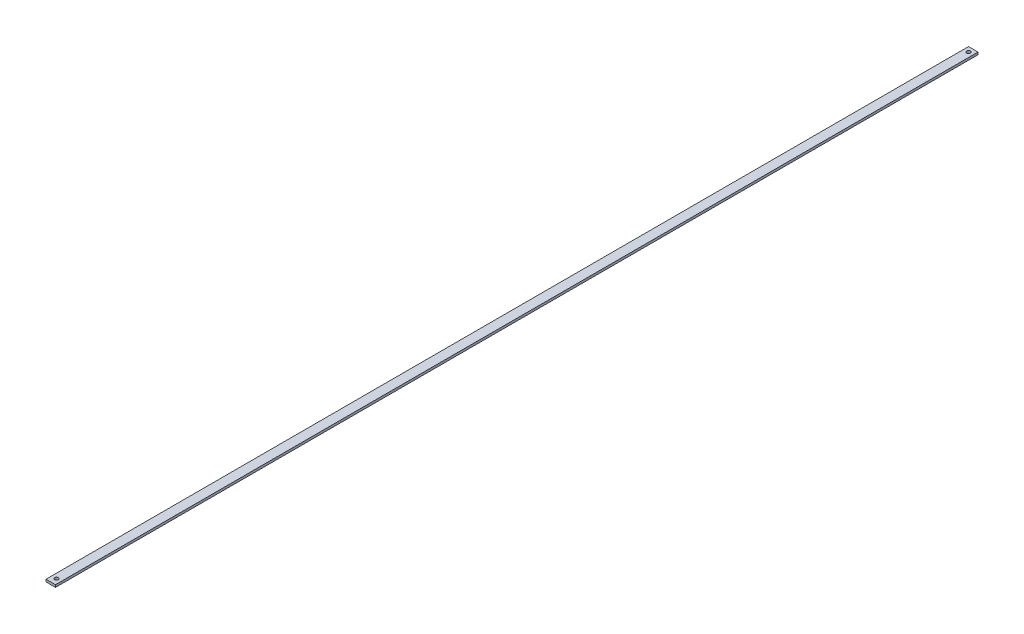
SolidWorks part; units mm, degrees
material "Plain Carbon Steel"
ref_plane "Front Plane" through (0, 0, 0) normal (0, 0, 1) x (1, 0, 0)
ref_plane "Top Plane" through (0, 0, 0) normal (0, 1, 0) x (1, 0, 0)
ref_plane "Right Plane" through (0, 0, 0) normal (1, 0, 0) x (0, 0, -1)
sketch "Sketch1" plane through (0, 0, 0) normal (0, 0, 1) x (1, 0, 0)
  line L1 (0, 0) -> (25.4, 0)
  line L2 (0, 0) -> (0, 6.35)
  line L3 (0, 6.35) -> (25.4, 6.35)
  line L4 (25.4, 0) -> (25.4, 6.35)
  dimension "D1" = 25.4
  dimension "D2" = 6.35
extrude "Boss-Extrude1" add sketch "Sketch1" along normal blind 2470.15
hole_wizard "X (0.397) Diameter Hole1" positions "Sketch3" profile "Sketch2" hole size "X" standard "ANSI Inch" end condition through all
sketch "Sketch3" plane through (0, 6.35, 0) normal (0, 1, 0) x (1, 0, 0)
  line L0 (12.7, 0) -> (12.7, -12.7) construction
  line L1 (25.4, 0) -> (0, 0) construction
  line L2 (12.7, -12.7) -> (25.4, -12.7) construction
  line L3 (25.4, -2470.15) -> (25.4, 0) construction
  point P0 (12.7, -12.7)
  dimension "D1" = 12.7
sketch "Sketch2" plane through (12.7, 6.35, 12.7) normal (1, 0, 0) x (0, 0, 1)
  line L0 (0, 0) -> (0, 6.35)
  line L1 (0, 6.35) -> (5.0419, 6.35)
  line L2 (5.0419, 6.35) -> (5.0419, 0)
  line L5 (5.0419, 0) -> (0, 0)
  line L11 (0, -6.35) -> (0, 107.95) construction
  dimension "Thru Hole Dia." = 10.0838
  dimension "Thru Hole Depth" = 6.35
hole_wizard "X (0.397) Diameter Hole2" positions "Sketch5" profile "Sketch4" hole size "X" standard "ANSI Inch" end condition through all
sketch "Sketch5" plane through (0, 0, 0) normal (0, -1, 0) x (-1, 0, 0)
  line L0 (-25.4, -2454.7515) -> (-12.7, -2454.7515) construction
  line L1 (-25.4, -2470.15) -> (-25.4, 0) construction
  line L2 (-12.7, -2454.7515) -> (0, -2454.7515) construction
  line L3 (0, -2470.15) -> (0, 0) construction
  point P0 (-12.7, -2454.7515)
sketch "Sketch4" plane through (12.7, 0, 2454.7515) normal (1, 0, 0) x (0, 0, -1)
  line L0 (0, 0) -> (0, 6.35)
  line L1 (0, 6.35) -> (5.0419, 6.35)
  line L2 (5.0419, 6.35) -> (5.0419, 0)
  line L5 (5.0419, 0) -> (0, 0)
  line L11 (0, -6.35) -> (0, 107.95) construction
  dimension "Thru Hole Dia." = 10.0838
  dimension "Thru Hole Depth" = 6.35
